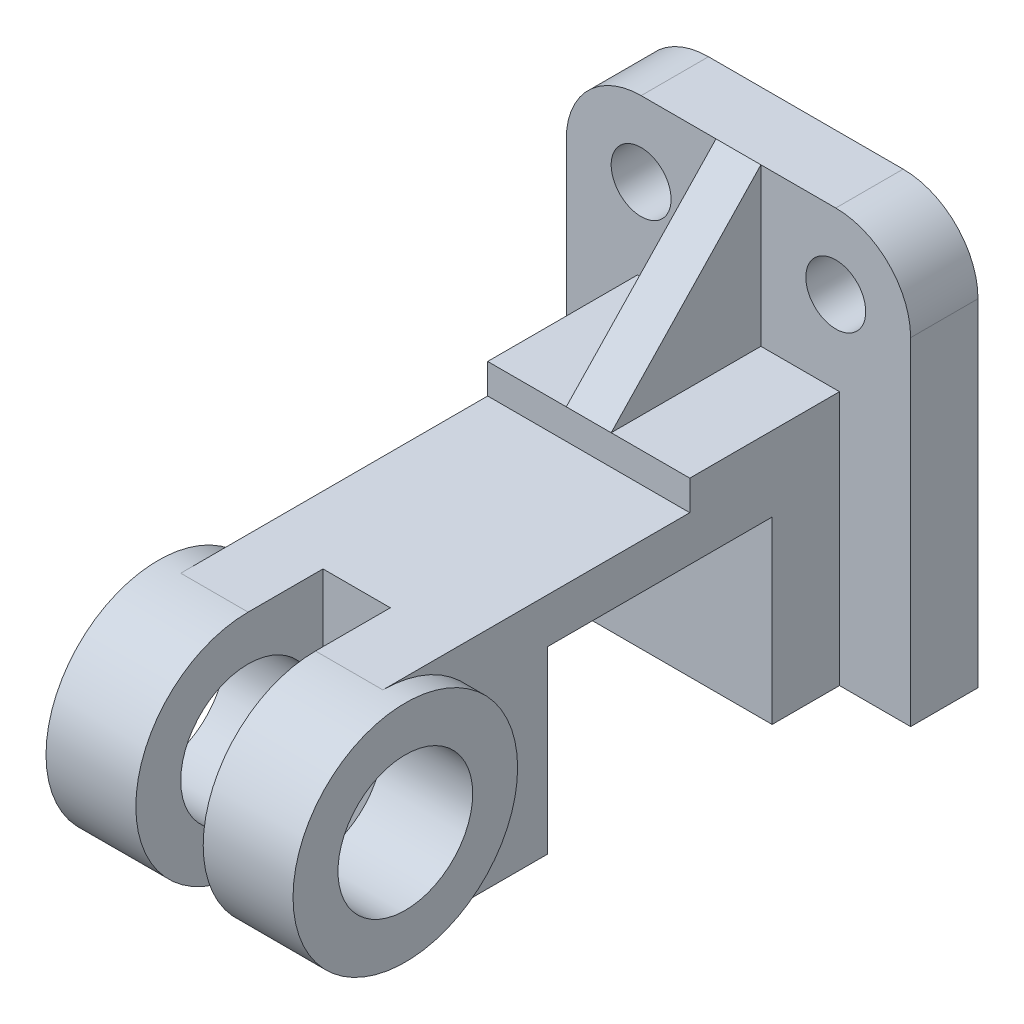
SolidWorks part; units mm, degrees
ref_plane "Front Plane" through (0, 0, 0) normal (0, 0, 1) x (1, 0, 0)
ref_plane "Top Plane" through (0, 0, 0) normal (0, 1, 0) x (1, 0, 0)
ref_plane "Right Plane" through (0, 0, 0) normal (1, 0, 0) x (0, 0, -1)
sketch "Sketch1" plane through (0, 0, 0) normal (1, 0, 0) x (0, 0, -1)
  line L1 (0, 0) -> (18, 0)
  line L2 (0, 0) -> (0, 110)
  line L3 (0, 110) -> (18, 110)
  line L4 (18, 0) -> (18, 110)
  dimension "D1" = 18
  dimension "D2" = 110
extrude "Boss-Extrude1" add sketch "Sketch1" along normal mid plane 92
sketch "Sketch2" plane through (0, 0, 0) normal (1, 0, 0) x (0, 0, -1)
  line L0 (0, 0) -> (-18, 0)
  line L1 (-18, 0) -> (-18, 48)
  line L2 (-18, 48) -> (-78, 48)
  line L3 (-78, 48) -> (-78, 0)
  line L4 (-78, 0) -> (-152, 0)
  line L5 (-152, 0) -> (-152, 60)
  line L6 (-152, 60) -> (-40, 60)
  line L7 (-40, 60) -> (-40, 68)
  line L8 (-40, 68) -> (0, 68)
  line L9 (0, 110) -> (0, 0) construction
  line L10 (0, 68) -> (0, 0)
  line L11 (18, 0) -> (18, 110) construction
  dimension "D1" = 60
  dimension "D2" = 18
  dimension "D3" = 170
  dimension "D4" = 8
  dimension "D5" = 12
  dimension "D6" = 60
  dimension "D7" = 40
extrude "Boss-Extrude2" add sketch "Sketch2" along normal mid plane 54
fillet "Fillet1" radius 30 2 edges at (0, 0, 152) (0, 60, 152)
sketch "Sketch3" plane through (27, 0, 0) normal (1, 0, 0) x (0, 0, -1)
  circle A0 centre (-122, 30) radius 30
  arc A1 (-122, 60) -> (-152, 30) centre (-122, 30) ccw construction
extrude "Boss-Extrude3" add sketch "Sketch3" along normal blind 6 and the other way blind 60
fillet "Fillet3" radius 20 2 edges at (-46, 110, -9) (46, 110, -9)
sketch "Sketch4" plane through (0, 60, 0) normal (0, 1, 0) x (1, 0, 0)
  line L0 (0, 0) -> (0, -130.3449) construction
  line L1 (-9, -102) -> (9, -102)
  line L2 (-9, -102) -> (-9, -152)
  line L3 (-9, -152) -> (9, -152)
  line L4 (9, -102) -> (9, -152)
  line L5 (27, -152) -> (-27, -152) construction
  dimension "D1" = 18
  dimension "D2" = 50
extrude "Cut-Extrude1" cut sketch "Sketch4" against normal through all
hole_wizard "Hole1" positions "Sketch5" profile "Sketch6" legacy end condition through all
sketch "Sketch5" plane through (33, 0, 0) normal (1, 0, 0) x (0, 0, -1)
  point P0 (-122, 30)
sketch "Sketch6" plane through (33, 30, 122) normal (0, 1, 0) x (0, 0, -1)
  line L0 (0, 0) -> (0, 79)
  line L1 (0, 79) -> (18, 79)
  line L2 (18, 79) -> (18, 0)
  line L3 (18, 0) -> (0, 0)
  line L4 (0, 110) -> (0, -10) construction
  dimension "Diameter" = 36
  dimension "Depth" = 79
hole_wizard "Hole2" positions "Sketch7" profile "Sketch8" legacy end condition through all
sketch "Sketch7" plane through (0, 0, 0) normal (0, 0, 1) x (1, 0, 0)
  point P0 (26, 90)
  point P3 (-26, 90)
  point P9 (0, 0)
  point P10 (-36, 100)
sketch "Sketch8" plane through (26, 90, 0) normal (1, 0, 0) x (0, -1, 0)
  line L0 (0, 0) -> (0, 18)
  line L1 (0, 18) -> (8, 18)
  line L2 (8, 18) -> (8, 0)
  line L3 (8, 0) -> (0, 0)
  line L4 (0, 110) -> (0, -10) construction
  dimension "Diameter" = 16
  dimension "Depth" = 18
sketch "Sketch9" plane through (0, 0, 0) normal (1, 0, 0) x (0, 0, -1)
  line L0 (0, 110) -> (-40, 68)
rib "Rib1" sketch "Sketch9" sketch "Sketch9" thickness 12 extrusion direction parallel to sketch draft on no parameters "D1"=12
